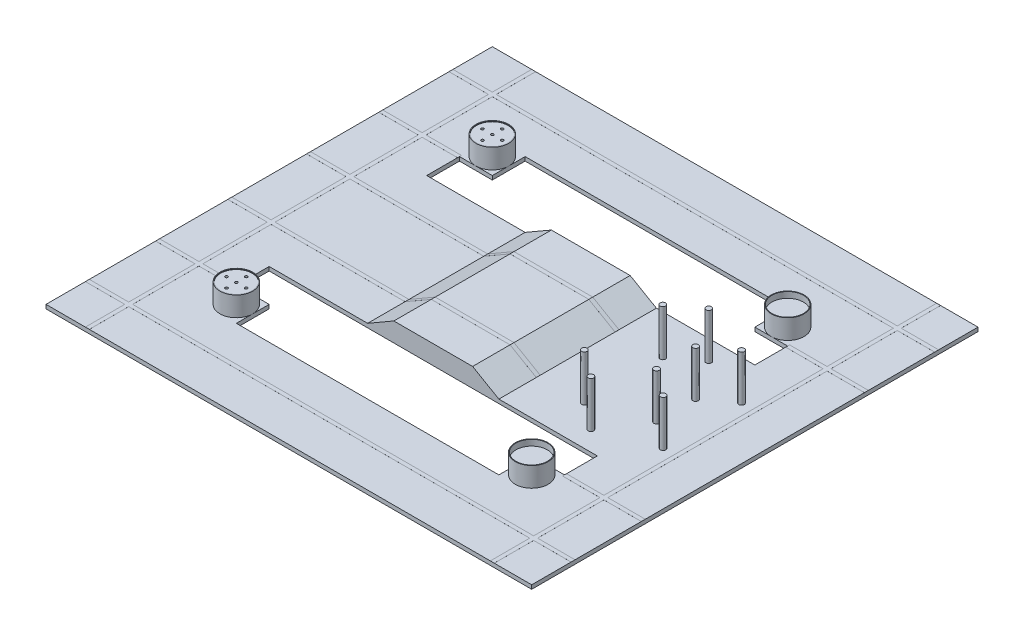
SolidWorks part; units mm, degrees
ref_plane "Front Plane" through (0, 0, 0) normal (0, 0, 1) x (1, 0, 0)
ref_plane "Top Plane" through (0, 0, 0) normal (0, 1, 0) x (1, 0, 0)
ref_plane "Right Plane" through (0, 0, 0) normal (1, 0, 0) x (0, 0, -1)
sketch "Sketch1" plane through (0, 0, 0) normal (0, 1, 0) x (1, 0, 0)
  line L0 (0, 1700) -> (0, -1700) construction
  line L1 (-1850, 1700) -> (1850, 1700)
  line L2 (-1850, 1700) -> (-1850, -1700)
  line L3 (-1850, -1700) -> (1850, -1700)
  line L4 (1850, 1700) -> (1850, -1700)
  line L5 (-1850, 0) -> (1850, 0) construction
  line L6 (-1250, -600) -> (1250, -600)
  line L7 (-1250, 1100) -> (1250, 1100)
  line L8 (-1250, 1100) -> (-1250, 600)
  line L9 (-1250, 600) -> (1250, 600)
  line L10 (1250, 1100) -> (1250, 600)
  line L11 (1250, -1100) -> (1250, -600)
  line L12 (-1250, -1100) -> (1250, -1100)
  line L13 (-1250, -1100) -> (-1250, -600)
  line L14 (1250, 850) -> (1000, 850)
  line L15 (-1250, 1100) -> (-1000, 1100)
  line L16 (-1250, 1100) -> (-1250, 850)
  line L17 (-1250, 850) -> (-1000, 850)
  line L18 (-1000, 1100) -> (-1000, 850)
  line L19 (1000, 1100) -> (1000, 850)
  line L20 (1000, -1100) -> (1000, -850)
  line L21 (1250, -850) -> (1000, -850)
  line L22 (-1250, -850) -> (-1000, -850)
  line L23 (-1000, -1100) -> (-1000, -850)
  dimension "D1" = 3700
  dimension "D2" = 3400
  dimension "D3" = 500
  dimension "D4" = 2500
  dimension "D5" = 600
  dimension "D6" = 600
  dimension "D7" = 250
  dimension "D8" = 250
extrude "Boss-Extrude1" add sketch "Sketch1" along normal blind 30 contours L4 L1 L2 L3 L7 L10 L9 L8 L12 L13 L6 L11 | L18 L7 L8 L17 | L7 L19 L14 L10 | L11 L21 L20 L12 | L12 L23 L22 L13 region at (0, 0, 0) region at (-1125, 0, 975) region at (1125, 0, 975) region at (-1125, 0, -975) region at (1125, 0, -975)
sketch "Sketch2" plane through (0, 0, 0) normal (0, 0, 1) x (1, 0, 0)
  line L0 (-500, 30) -> (-300, 145.4701)
  line L1 (-1850, 30) -> (1850, 30) construction
  line L2 (-300, 145.4701) -> (300, 145.4701)
  line L3 (300, 145.4701) -> (500, 30)
  line L4 (500, 30) -> (-500, 30)
  line L5 (0, 145.4701) -> (0, 30) construction
  dimension "D1" = 200
  dimension "D2" = 600
  dimension "D3" = 30
extrude "Boss-Extrude2" add sketch "Sketch2" along normal mid plane 1200
sketch "Sketch3" plane through (0, 30, 0) normal (0, 1, 0) x (1, 0, 0)
  line L0 (-1125, 850) -> (-1125, 1042.2639) construction
  line L1 (-1250, 850) -> (-1000, 850) construction
  line L2 (-1000, 975) -> (-1165.3308, 975) construction
  line L3 (-1000, 1100) -> (-1000, 850) construction
  circle A0 centre (-1125, 975) radius 125
extrude "Boss-Extrude3" add sketch "Sketch3" along normal blind 150
sketch "Sketch4" plane through (0, 180, 0) normal (0, 1, 0) x (1, 0, 0)
  circle A0 centre (-1125, 975) radius 120
  dimension "D1" = 240
extrude "Cut-Extrude1" cut sketch "Sketch4" against normal blind 5
sketch "Sketch5" plane through (0, 175, 0) normal (0, 1, 0) x (1, 0, 0)
  line L0 (-1005, 975) -> (-1245, 975) construction
  line L1 (-1125, 1095) -> (-1125, 855) construction
  circle A0 centre (-1125, 975) radius 120 construction
  circle A1 centre (-1125, 975) radius 120 construction
  circle A2 centre (-1125, 975) radius 10
  circle A3 centre (-1050, 975) radius 10
  circle A4 centre (-1125, 900) radius 10
  circle A5 centre (-1200, 975) radius 10
  circle A6 centre (-1125, 1050) radius 10
  dimension "D1" = 20
  dimension "D2" = 75
  dimension "D3" = 75
  dimension "D4" = 75
  dimension "D5" = 75
extrude "Cut-Extrude2" cut sketch "Sketch5" against normal blind 20
mirror "Mirror2" about plane through (0, 0, 0) normal (0, 0, 1) of "Boss-Extrude3", "Cut-Extrude1", "Cut-Extrude2"
mirror "Mirror3" about plane through (0, 0, 0) normal (1, 0, 0) of "Mirror2"
sketch "Sketch6" plane through (0, 175, 0) normal (0, 1, 0) x (1, 0, 0)
  circle A0 centre (1125, 975) radius 120
extrude "Cut-Extrude3" cut sketch "Sketch6" against normal blind 40
mirror "Mirror4" about plane through (0, 0, 0) normal (0, 0, 1) of "Cut-Extrude3"
sketch "Sketch7" plane through (0, 30, 0) normal (0, 1, 0) x (1, 0, 0)
  line L1 (-1850, 1700) -> (-1550, 1700)
  line L2 (-1850, 1700) -> (-1850, 1400)
  line L3 (-1850, 1400) -> (-1550, 1400)
  line L4 (-1550, 1700) -> (-1550, 1400)
  line L5 (-1850, -1700) -> (-1550, -1700)
  line L6 (-1850, -1700) -> (-1850, -1400)
  line L7 (-1850, -1400) -> (-1550, -1400)
  line L8 (-1550, -1700) -> (-1550, -1400)
  dimension "D1" = 300
extrude "Boss-Extrude4" add sketch "Sketch7" along normal blind 0.1
sketch "Sketch8" plane through (0, 30, 0) normal (0, 1, 0) x (1, 0, 0)
  line L0 (-1850, 1385) -> (1850, 1385)
  line L1 (-1850, 1400) -> (-1850, -1400) construction
  line L2 (1850, 1700) -> (1850, -1700) construction
  line L3 (-1535, 1700) -> (-1535, -1700)
  line L4 (-1550, 1700) -> (1850, 1700) construction
  line L5 (-1550, -1700) -> (1850, -1700) construction
  line L6 (1550, 1700) -> (1550, -1700)
  line L7 (-1250, 850) -> (-1850, 850)
  line L8 (-1850, 300) -> (500, 300)
  line L9 (-1850, -300) -> (500, -300)
  line L10 (-1850, -1385) -> (1850, -1385)
  line L11 (-1250, -850) -> (-1850, -850)
  line L12 (-1850, 1400) -> (-1550, 1400) construction
  line L13 (-1550, 1400) -> (-1550, 1700) construction
  line L14 (-1250, -600) -> (-500, -600) construction
  line L15 (-1250, 600) -> (-500, 600) construction
  line L16 (-1550, -1400) -> (-1850, -1400) construction
  line L17 (1250, 850) -> (1850, 850)
  line L18 (1250, -850) -> (1850, -850)
  line L19 (500, 600) -> (500, -600) construction
  dimension "D1" = 15
  dimension "D2" = 15
  dimension "D3" = 300
  dimension "D4" = 300
  dimension "D5" = 300
  dimension "D6" = 15
extrude "Extrude-Thin1" add sketch "Sketch8" along normal blind 0.2 thin contours L0 | L3 | L7 | L8 | L9 | L11 | L10 | L6 | L17 | L18 thin type mid plane wall 30
sketch "Sketch9" plane through (-137.9904, 239.0064, 0) normal (-0.5, 0.866, 0) x (0.866, 0.5, 0)
  line L0 (-417.8127, 300) -> (-187.0726, 300)
  line L1 (-417.8127, 285) -> (-417.8127, 315) construction
  line L2 (-187.0726, -600) -> (-187.0726, 600) construction
  line L3 (-417.8127, -300) -> (-187.0726, -300)
  line L4 (-417.8127, -315) -> (-417.8127, -285) construction
extrude "Extrude-Thin2" add sketch "Sketch9" along normal blind 0.1 thin contours L0 | L3 thin type mid plane wall 30
sketch "Sketch10" plane through (0, 145.4701, 0) normal (0, 1, 0) x (1, 0, 0)
  line L0 (-300, 300) -> (300, 300)
  line L1 (-300, 315) -> (-300, 285) construction
  line L2 (300, -600) -> (300, 600) construction
  line L3 (-300, -300) -> (300, -300)
  line L4 (-300, -285) -> (-300, -315) construction
extrude "Extrude-Thin3" add sketch "Sketch10" along normal blind 0.1 thin contours L0 | L3 thin type mid plane wall 30
mirror "Mirror5" about plane through (0, 0, 0) normal (1, 0, 0) of "Extrude-Thin2"
sketch "Sketch11" plane through (0, 30, 0) normal (0, 1, 0) x (1, 0, 0)
  line L0 (500, 0) -> (1467.7975, 0) construction
  line L1 (500, -285) -> (500, 285) construction
  line L2 (500, -600) -> (500, -315) construction
  circle A0 centre (850, -298.837) radius 21
  circle A1 centre (1050, -448.837) radius 21
  circle A2 centre (1450, -298.837) radius 21
  circle A3 centre (1250, -148.837) radius 21
  dimension "D1" = 42
  dimension "D2" = 350
  dimension "D3" = 200
  dimension "D4" = 200
  dimension "D5" = 200
  dimension "D6" = 150
  dimension "D7" = 150
  dimension "D8" = 150
extrude "Boss-Extrude5" add sketch "Sketch11" along normal blind 350
mirror "Mirror6" about plane through (0, 0, 0) normal (0, 0, 1) of "Boss-Extrude5"
sketch "Sketch12" plane through (0, 30, 0) normal (0, 1, 0) x (1, 0, 0)
  line L1 (500, -600) -> (-500, -600)
  line L2 (500, -600) -> (500, 600)
  line L3 (500, 600) -> (-500, 600)
  line L4 (-500, -600) -> (-500, 600)
